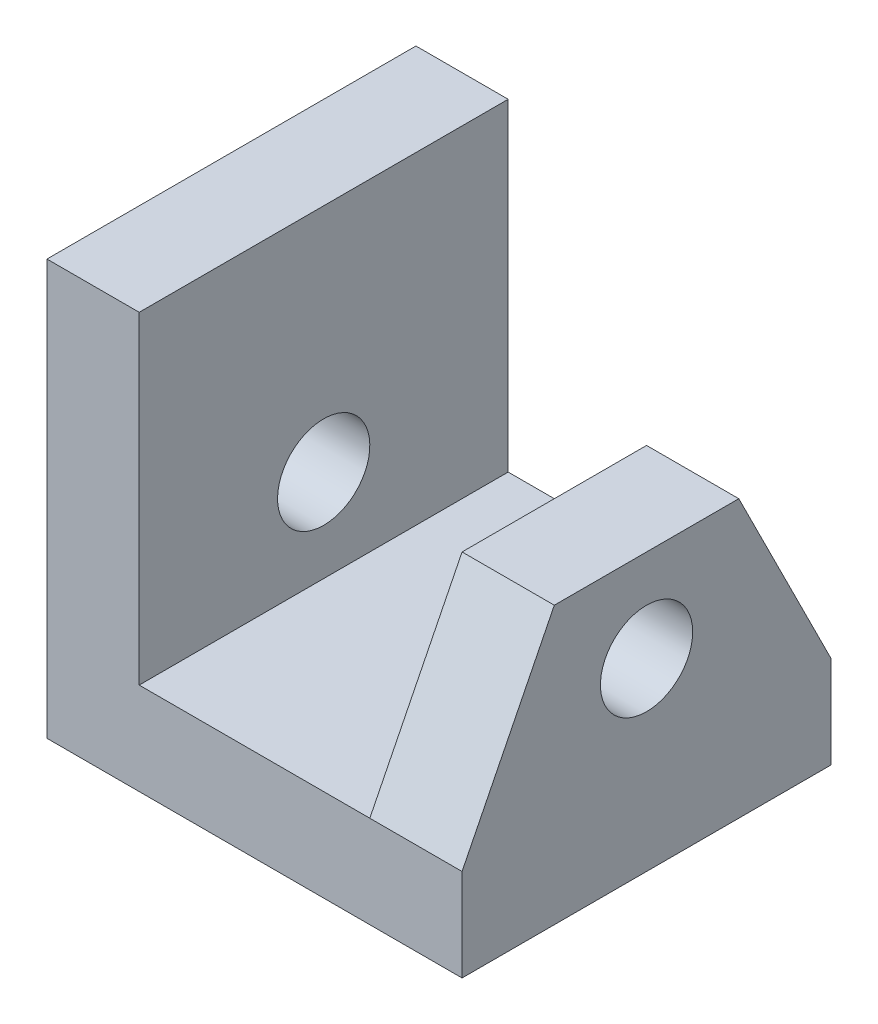
SolidWorks part; units mm, degrees
ref_plane "정면" through (0, 0, 0) normal (0, 0, 1) x (1, 0, 0)
ref_plane "윗면" through (0, 0, 0) normal (0, 1, 0) x (1, 0, 0)
ref_plane "우측면" through (0, 0, 0) normal (1, 0, 0) x (0, 0, -1)
sketch "스케치1" plane through (0, 0, 0) normal (0, 0, 1) x (1, 0, 0)
  line L0 (0, 0) -> (45, 0)
  line L1 (45, 0) -> (45, 10)
  line L2 (45, 10) -> (10, 10)
  line L3 (10, 10) -> (10, 45)
  line L4 (10, 45) -> (0, 45)
  line L5 (0, 45) -> (0, 0)
  line L6 (45, 10) -> (45, 30)
  line L7 (45, 30) -> (35, 30)
  line L8 (35, 30) -> (35, 10)
  dimension "D1" = 45
  dimension "D2" = 10
  dimension "D3" = 10
  dimension "D4" = 35
  dimension "D5" = 20
  dimension "D6" = 10
  dimension "D7" = 45
extrude "보스-돌출1" add sketch "스케치1" along normal mid plane 40 contours L4 L5 L0 L1 L2 L3 region at (0.6364, 22.5, 0)
extrude "보스-돌출2" add sketch "스케치1<3>" along normal mid plane 40 contours L7 L8 L2 L6 region at (40, 20, 0)
sketch "스케치1<3>" plane through (0, 0, 0) normal (0, 0, 1) x (1, 0, 0) same geometry as "스케치1"
sketch "스케치2" plane through (45, 0, 0) normal (1, 0, 0) x (0, 0, -1)
  line L0 (-10, 30) -> (-20, 10)
  line L1 (-5, 30) -> (10, 30) construction
  line L2 (-20, 0) -> (-20, 10) construction
  line L3 (0, 45) -> (0, 0) construction
  circle A0 centre (0, 20) radius 5
  line M3 (20, 30) -> (-20, 30)
  line M4 (-20, 30) -> (-20, 0)
  dimension "D3" = 10
  dimension "D1" = 10
  dimension "D2" = 10
  dimension "D4" = 20
extrude "컷-돌출1" cut sketch "스케치2" against normal blind 10 contours A0
sketch "스케치4" plane through (45, 0, 0) normal (1, 0, 0) x (0, 0, -1)
  line L0 (-10, 30) -> (-20, 30)
  line L1 (-20, 30) -> (-20, 10)
extrude "컷-돌출2" cut sketch "스케치2<5>" against normal blind 10 and the other way through all contours L0 M3 M4 region at (45, 23.3333, 16.6667)
sketch "스케치2<5>" plane through (45, 0, 0) normal (1, 0, 0) x (0, 0, -1) same geometry as "스케치2"
sketch "스케치7" plane through (45, 0, 0) normal (1, 0, 0) x (0, 0, -1)
  line L0 (10, 30) -> (20, 10)
  line L1 (-10, 30) -> (20, 30) construction
  line L2 (20, 0) -> (20, 30) construction
  line M3 (20, 30) -> (-10, 30)
  line M7 (20, 0) -> (20, 30)
  dimension "D1" = 10
  dimension "D2" = 10
extrude "컷-돌출3" cut sketch "스케치7" against normal blind 10 and the other way through all contours L0 M3 M7 region at (45, 23.3333, -16.6667)
sketch "스케치9" plane through (0, 0, 0) normal (-1, 0, 0) x (0, 0, 1)
  circle A0 centre (0, 20) radius 5
  dimension "D1" = 10
extrude "컷-돌출4" cut sketch "스케치9" against normal blind 10 contours A0 | A0 region at (0, 20, 0)
